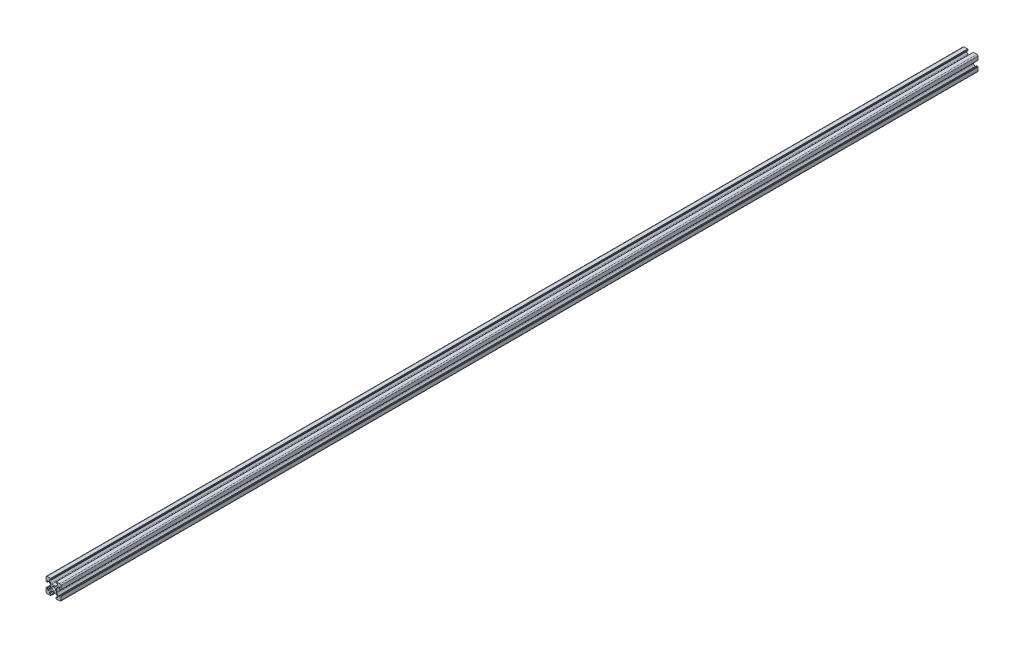
SolidWorks part; units mm, degrees
ref_plane "前视基准面" through (0, 0, 0) normal (0, 0, 1) x (1, 0, 0)
ref_plane "上视基准面" through (0, 0, 0) normal (0, 1, 0) x (1, 0, 0)
ref_plane "右视基准面" through (0, 0, 0) normal (1, 0, 0) x (0, 0, -1)
sketch "草图1" plane through (0, 0, 0) normal (0, 0, 1) x (1, 0, 0)
  line L0 (0, 0) -> (0, 5.5) construction
  line L1 (-8.5023, -10.0023) -> (-3.85, -10.0023)
  line L2 (-10.0023, -8.5023) -> (-10.0023, -3.85)
  line L3 (-8.5023, 10.0023) -> (-3.85, 10.0023)
  line L4 (10.0023, -8.5023) -> (10.0023, -3.85)
  line L5 (-10.0023, -10.0023) -> (10.0023, 10.0023) construction
  line L6 (-10.0023, 10.0023) -> (10.0023, -10.0023) construction
  line L7 (-2.218, -3.9) -> (2.218, -3.9)
  line L8 (-3.9, -2.218) -> (-3.9, 2.218)
  line L9 (-2.218, 3.9) -> (2.218, 3.9)
  line L10 (3.9, -2.218) -> (3.9, 2.218)
  line L11 (-3.9, -3.9) -> (3.9, 3.9) construction
  line L12 (-3.9, 3.9) -> (3.9, -3.9) construction
  line L13 (-5.25, -8.2) -> (-3.35, -8.2)
  line L14 (-8.2, -5.25) -> (-8.2, -3.35)
  line L15 (-5.25, 8.2) -> (-3.35, 8.2)
  line L16 (8.2, -5.25) -> (8.2, -3.35)
  line L17 (-8.2, -8.2) -> (8.2, 8.2) construction
  line L18 (-8.2, 8.2) -> (8.2, -8.2) construction
  line L19 (-7.95, 5.5) -> (-6.6642, 5.5)
  line L20 (0, 0) -> (5.5, 0) construction
  line L23 (-5.5, 7.95) -> (-5.5, 6.6642)
  line L26 (0, 0) -> (-0.5303, 0.5303)
  line L27 (3.2787, 4.3393) -> (5.4268, 6.4874)
  line L28 (0, 0) -> (0.5303, -0.5303)
  line L29 (5.5, 6.6642) -> (5.5, 7.95)
  line L30 (4.3393, 3.2787) -> (6.4874, 5.4268)
  line L31 (6.6642, 5.5) -> (7.95, 5.5)
  line L32 (4.3393, -3.2787) -> (6.4874, -5.4268)
  line L33 (3.2787, -4.3393) -> (5.4268, -6.4874)
  line L34 (-3.2787, -4.3393) -> (-5.4268, -6.4874)
  line L35 (-4.3393, -3.2787) -> (-6.4874, -5.4268)
  line L36 (-4.3393, 3.2787) -> (-6.4874, 5.4268)
  line L37 (-3.2787, 4.3393) -> (-5.4268, 6.4874)
  line L38 (3.1, -8.45) -> (3.1, -9.2523)
  line L39 (8.45, 3.1) -> (9.2523, 3.1)
  line L40 (-5.5, -6.6642) -> (-5.5, -7.95)
  line L41 (-6.6642, -5.5) -> (-7.95, -5.5)
  line L42 (5.5, -6.6642) -> (5.5, -7.95)
  line L43 (6.6642, -5.5) -> (7.95, -5.5)
  line L44 (9.2523, -3.1) -> (8.45, -3.1)
  line L46 (10.0023, 3.85) -> (10.0023, 8.5023)
  line L47 (8.2, 3.35) -> (8.2, 5.25)
  line L48 (-3.1, -9.2523) -> (-3.1, -8.45)
  line L49 (-8.45, -3.1) -> (-9.2523, -3.1)
  line L50 (-9.2523, 3.1) -> (-8.45, 3.1)
  line L51 (-3.1, 8.45) -> (-3.1, 9.2523)
  line L52 (3.1, 9.2523) -> (3.1, 8.45)
  line L53 (3.85, 10.0023) -> (8.5023, 10.0023)
  line L54 (3.35, 8.2) -> (5.25, 8.2)
  line L55 (-10.0023, 3.85) -> (-10.0023, 8.5023)
  line L56 (-8.2, 3.35) -> (-8.2, 5.25)
  line L57 (3.35, -8.2) -> (5.25, -8.2)
  line L58 (3.85, -10.0023) -> (8.5023, -10.0023)
  line L59 (9.7523, -3.6) -> (9.5023, -3.6)
  line L61 (9.7523, 3.6) -> (9.5023, 3.6)
  line L62 (9.5023, -3.6) -> (9.5023, -3.35)
  line L63 (3.6, -9.7523) -> (3.6, -9.5023)
  line L64 (3.35, -9.5023) -> (3.6, -9.5023)
  line L65 (9.5023, 3.35) -> (9.5023, 3.6)
  line L66 (-3.6, -9.5023) -> (-3.35, -9.5023)
  line L67 (-3.6, -9.7523) -> (-3.6, -9.5023)
  line L68 (-9.7523, -3.6) -> (-9.5023, -3.6)
  line L69 (-9.5023, -3.35) -> (-9.5023, -3.6)
  line L70 (-9.5023, 3.6) -> (-9.5023, 3.35)
  line L71 (-9.7523, 3.6) -> (-9.5023, 3.6)
  line L72 (-3.6, 9.7523) -> (-3.6, 9.5023)
  line L73 (-3.35, 9.5023) -> (-3.6, 9.5023)
  line L74 (3.6, 9.5023) -> (3.35, 9.5023)
  line L75 (3.6, 9.7523) -> (3.6, 9.5023)
  circle A0 centre (0, 0) radius 2.5
  arc A1 (10.0023, 8.5023) -> (8.5023, 10.0023) centre (8.5023, 8.5023) ccw
  arc A2 (8.5023, -10.0023) -> (10.0023, -8.5023) centre (8.5023, -8.5023) ccw
  arc A3 (-10.0023, -8.5023) -> (-8.5023, -10.0023) centre (-8.5023, -8.5023) ccw
  arc A4 (-10.0023, 8.5023) -> (-8.5023, 10.0023) centre (-8.5023, 8.5023) cw
  arc A5 (-9.5023, -3.35) -> (-9.2523, -3.1) centre (-9.2523, -3.35) cw
  arc A6 (-9.7523, -3.6) -> (-10.0023, -3.85) centre (-9.7523, -3.85) ccw
  arc A7 (-8.45, -3.1) -> (-8.2, -3.35) centre (-8.45, -3.35) cw
  arc A8 (-7.95, -5.5) -> (-8.2, -5.25) centre (-7.95, -5.25) cw
  arc A9 (-6.4874, -5.4268) -> (-6.6642, -5.5) centre (-6.6642, -5.25) cw
  arc A10 (-5.4268, -6.4874) -> (-5.5, -6.6642) centre (-5.25, -6.6642) ccw
  arc A11 (-5.5, -7.95) -> (-5.25, -8.2) centre (-5.25, -7.95) ccw
  arc A12 (-3.6, -9.7523) -> (-3.85, -10.0023) centre (-3.85, -9.7523) cw
  arc A13 (-3.35, -9.5023) -> (-3.1, -9.2523) centre (-3.35, -9.2523) ccw
  arc A14 (-3.1, -8.45) -> (-3.35, -8.2) centre (-3.35, -8.45) ccw
  arc A15 (3.1, -8.45) -> (3.35, -8.2) centre (3.35, -8.45) cw
  arc A16 (5.5, -7.95) -> (5.25, -8.2) centre (5.25, -7.95) cw
  arc A17 (5.4268, -6.4874) -> (5.5, -6.6642) centre (5.25, -6.6642) cw
  arc A18 (6.4874, -5.4268) -> (6.6642, -5.5) centre (6.6642, -5.25) ccw
  arc A19 (7.95, -5.5) -> (8.2, -5.25) centre (7.95, -5.25) ccw
  arc A20 (8.45, -3.1) -> (8.2, -3.35) centre (8.45, -3.35) ccw
  arc A21 (9.5023, -3.35) -> (9.2523, -3.1) centre (9.2523, -3.35) ccw
  arc A22 (9.7523, -3.6) -> (10.0023, -3.85) centre (9.7523, -3.85) cw
  arc A23 (3.35, -9.5023) -> (3.1, -9.2523) centre (3.35, -9.2523) cw
  arc A24 (3.6, -9.7523) -> (3.85, -10.0023) centre (3.85, -9.7523) ccw
  arc A25 (7.95, 5.5) -> (8.2, 5.25) centre (7.95, 5.25) cw
  arc A26 (8.2, 3.35) -> (8.45, 3.1) centre (8.45, 3.35) ccw
  arc A27 (9.5023, 3.35) -> (9.2523, 3.1) centre (9.2523, 3.35) cw
  arc A28 (9.7523, 3.6) -> (10.0023, 3.85) centre (9.7523, 3.85) ccw
  arc A29 (6.6642, 5.5) -> (6.4874, 5.4268) centre (6.6642, 5.25) ccw
  arc A30 (5.4268, 6.4874) -> (5.5, 6.6642) centre (5.25, 6.6642) ccw
  arc A31 (5.5, 7.95) -> (5.25, 8.2) centre (5.25, 7.95) ccw
  arc A32 (3.1, 8.45) -> (3.35, 8.2) centre (3.35, 8.45) ccw
  arc A33 (3.6, 9.7523) -> (3.85, 10.0023) centre (3.85, 9.7523) cw
  arc A34 (3.35, 9.5023) -> (3.1, 9.2523) centre (3.35, 9.2523) ccw
  arc A35 (-9.7523, 3.6) -> (-10.0023, 3.85) centre (-9.7523, 3.85) cw
  arc A36 (-9.5023, 3.35) -> (-9.2523, 3.1) centre (-9.2523, 3.35) ccw
  arc A37 (-8.45, 3.1) -> (-8.2, 3.35) centre (-8.45, 3.35) ccw
  arc A38 (-8.2, 5.25) -> (-7.95, 5.5) centre (-7.95, 5.25) cw
  arc A39 (-6.4874, 5.4268) -> (-6.6642, 5.5) centre (-6.6642, 5.25) ccw
  arc A40 (-5.4268, 6.4874) -> (-5.5, 6.6642) centre (-5.25, 6.6642) cw
  arc A41 (-5.5, 7.95) -> (-5.25, 8.2) centre (-5.25, 7.95) cw
  arc A42 (-3.1, 8.45) -> (-3.35, 8.2) centre (-3.35, 8.45) cw
  arc A43 (-3.1, 9.2523) -> (-3.35, 9.5023) centre (-3.35, 9.2523) ccw
  arc A44 (-3.6, 9.7523) -> (-3.85, 10.0023) centre (-3.85, 9.7523) ccw
  arc A45 (-4.3393, 3.2787) -> (-3.9, 2.218) centre (-5.4, 2.218) cw
  arc A46 (-3.2787, 4.3393) -> (-2.218, 3.9) centre (-2.218, 5.4) ccw
  arc A47 (3.2787, 4.3393) -> (2.218, 3.9) centre (2.218, 5.4) cw
  arc A48 (4.3393, 3.2787) -> (3.9, 2.218) centre (5.4, 2.218) ccw
  arc A49 (4.3393, -3.2787) -> (3.9, -2.218) centre (5.4, -2.218) cw
  arc A50 (3.2787, -4.3393) -> (2.218, -3.9) centre (2.218, -5.4) ccw
  arc A51 (-4.3393, -3.2787) -> (-3.9, -2.218) centre (-5.4, -2.218) ccw
  arc A52 (-2.218, -3.9) -> (-3.2787, -4.3393) centre (-2.218, -5.4) ccw
  point P0 (0, 0)
  point P7 (10.0023, 0)
  point P62 (0, 0)
  point P76 (0, 0)
  point P92 (-8.2, -5.5)
  point P99 (0, 0)
  point P106 (-5.5, -8.2)
  point P117 (5.5, -8.2)
  point P124 (8.2, -5.5)
  point P137 (8.2, 5.5)
  point P140 (8.2, 3.1)
  point P147 (6.5607, 5.5)
  point P152 (5.5, 8.2)
  point P167 (-8.2, 5.5)
  point P174 (-5.5, 8.2)
  dimension "D1" = 1.5
  dimension "D5" = 0.25
  dimension "D6" = 1.5
  dimension "D2" = 4
  dimension "D3" = 4
  dimension "D4" = 4
extrude "凸台-拉伸1" add sketch "草图1" along normal blind 1220 contours A52 L7 A50 L33 A17 L42 A16 L57 A15 L38 A23 L64 L63 A24 L58 A2 L4 A22 L59 L62 A21 L44 A20 L16 A19 L43 A18 L32 A49 L10 A48 L30 A29 L31 A25 L47 A26 L39 A27 L65 L61 A28 L46 A1 L53 A33 L75 L74 A34 L52 A32 region at (-9.3629, -9.3629, 0)
